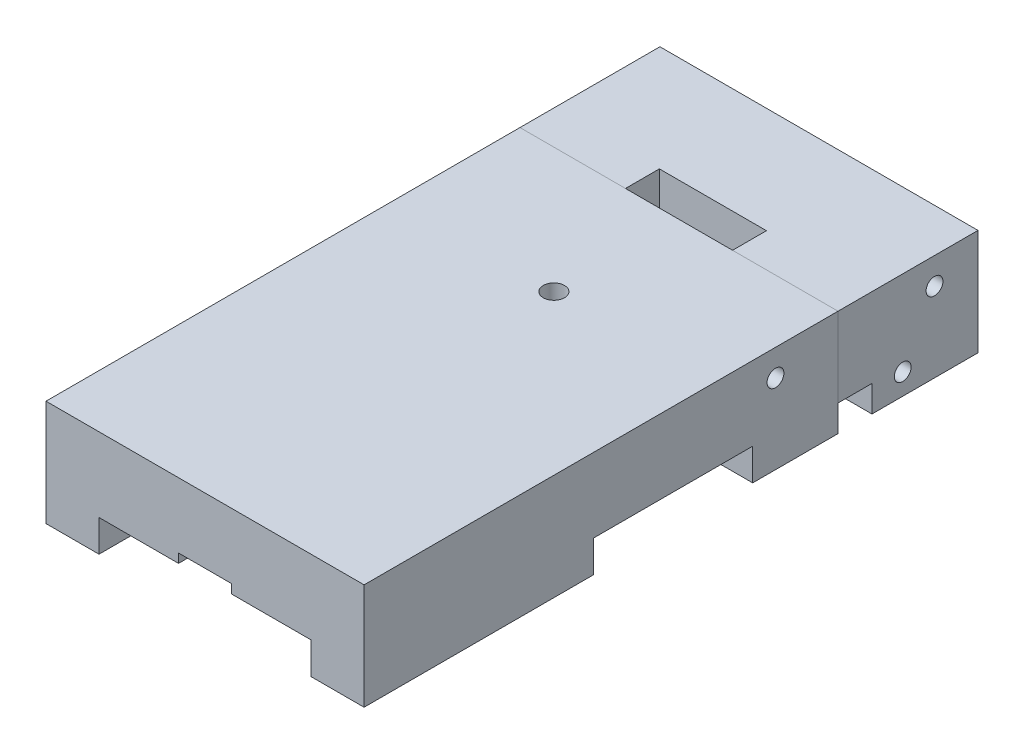
SolidWorks part; units mm, degrees
material "Nylon 6/10"
ref_plane "Front Plane" through (0, 0, 0) normal (0, 0, 1) x (1, 0, 0)
ref_plane "Top Plane" through (0, 0, 0) normal (0, 1, 0) x (1, 0, 0)
ref_plane "Right Plane" through (0, 0, 0) normal (1, 0, 0) x (0, 0, -1)
sketch "Sketch1" plane through (0, 0, 0) normal (0, 1, 0) x (1, 0, 0)
  line L1 (-38.1, -73.533) -> (38.1, -73.533)
  line L2 (-38.1, -73.533) -> (-38.1, 73.533)
  line L3 (-38.1, 73.533) -> (38.1, 73.533)
  line L4 (38.1, -73.533) -> (38.1, 73.533)
  line L5 (-38.1, -73.533) -> (38.1, 73.533) construction
  line L6 (-38.1, 73.533) -> (38.1, -73.533) construction
  point P0 (0, 0)
  dimension "D1" = 76.2
  dimension "D2" = 147.066
extrude "Boss-Extrude1" add sketch "Sketch1" along normal blind 12.7 and the other way blind 12.7
sketch "Sketch2" plane through (0, 0, -73.533) normal (0, 0, -1) x (-1, 0, 0)
  line L1 (-38.1, -12.7) -> (38.1, -12.7) construction
  circle A0 centre (0, -12.7) radius 4.7625
  dimension "D1" = 9.525
extrude "Cut-Extrude1" cut sketch "Sketch2" against normal blind 25.4
ref_plane "Plane1" through (0, -12.7, 0) normal (0, -1, 0) x (-1, 0, 0)
sketch "Sketch3" plane through (0, -12.7, 0) normal (0, -1, 0) x (-1, 0, 0)
  line L0 (10.922, 19.558) -> (44.45, 19.558)
  line L1 (-19.05, -83.058) -> (19.05, -83.058)
  line L2 (-25.4, -76.708) -> (-25.4, -18.542)
  line L3 (0, 0) -> (0, 102.0916) construction
  line L4 (25.4, -76.708) -> (25.4, -18.542)
  line L5 (-10.922, 19.558) -> (-10.922, 40.005)
  line L6 (25.4, -18.542) -> (44.45, -18.542)
  line L7 (-10.922, 40.005) -> (10.922, 40.005)
  line L8 (10.922, 19.558) -> (10.922, 40.005)
  line L10 (-44.45, -18.542) -> (-25.4, -18.542)
  line L11 (-44.45, -18.542) -> (-44.45, 19.558)
  line L12 (-44.45, 19.558) -> (-10.922, 19.558)
  line L13 (44.45, -18.542) -> (44.45, 19.558)
  line L14 (4.7625, 73.533) -> (4.7625, 48.133)
  line L15 (4.7625, 48.133) -> (-4.7625, 48.133)
  line L16 (-4.7625, 48.133) -> (-4.7625, 73.533)
  line L17 (-4.7625, 73.533) -> (-38.1, 73.533)
  line L18 (-38.1, 73.533) -> (-38.1, -73.533)
  line L19 (-38.1, -73.533) -> (38.1, -73.533)
  line L20 (38.1, -73.533) -> (38.1, 73.533)
  line L21 (38.1, 73.533) -> (4.7625, 73.533)
  line L25 (-4.7625, 73.533) -> (-38.1, 73.533) construction
  line L26 (-38.1, 73.533) -> (-38.1, -73.533) construction
  line L27 (-38.1, -73.533) -> (38.1, -73.533) construction
  line L28 (38.1, -73.533) -> (38.1, 73.533) construction
  line L29 (38.1, 73.533) -> (4.7625, 73.533) construction
  arc A0 (-25.4, -76.708) -> (-19.05, -83.058) centre (-19.05, -76.708) ccw
  arc A1 (19.05, -83.058) -> (25.4, -76.708) centre (19.05, -76.708) ccw
  dimension "D5" = 6.35
  dimension "D6" = 21.844
  dimension "D8" = 19.05
  dimension "D9" = 20.447
  dimension "D2" = 25.4
  dimension "D3" = 25.4
  dimension "D4" = 9.525
  dimension "D7" = 38.1
  dimension "D10" = 53.975
  dimension "D1" = 0
extrude "Cut-Extrude2" cut sketch "Sketch3" against normal blind 7.62
sketch "Sketch5" plane through (0, 0, 0) normal (0, 1, 0) x (1, 0, 0)
  line L0 (-4.7625, 73.533) -> (-38.1, 73.533) construction
  line L1 (12.827, 48.133) -> (-12.827, 48.133)
  line L2 (12.827, 40.005) -> (12.827, 48.133)
  line L3 (12.827, 40.005) -> (-12.827, 40.005)
  line L4 (0, 0) -> (0, 121.8983) construction
  line L6 (-12.827, 40.005) -> (-12.827, 48.133)
  point P17 (12.827, 40.005)
  point P20 (12.827, 48.133)
  dimension "D1" = 8.128
  dimension "D2" = 25.654
  dimension "D4" = 25.4
extrude "Cut-Extrude4" cut sketch "Sketch5" along normal through all and the other way through all
hole_wizard "1/4-20 Tapped Hole1" positions "Sketch8" profile "Sketch7" tap size "1/4-20" standard "ANSI Inch"
sketch "Sketch8" plane through (-11.0345, 12.7, 14.5475) normal (0, -1, 0) x (-1, 0, 0)
  line L1 (-23.8615, 62.6805) -> (1.7925, 62.6805) construction
  point P0 (-11.0345, 24.5805)
  dimension "D1" = 38.1
  dimension "D2" = 0
sketch "Sketch7" plane through (0, 12.7, -10.033) normal (1, 0, 0) x (0, 0, 1)
  line L0 (0, 0) -> (0, 20.5838)
  line L1 (0, 20.5838) -> (2.5527, 19.05)
  line L2 (2.5527, 19.05) -> (2.5527, 0)
  line L5 (2.5527, 0) -> (0, 0)
  line L10 (0, 20.5838) -> (-2.5527, 19.05) construction
  line L11 (0, -6.35) -> (0, 107.95) construction
  dimension "Tap Drill Dia." = 5.1054
  dimension "Tap Drill Depth" = 19.05
  dimension "Drill Angle" = 118
cosmetic thread "Hole Thread2" parameters "D1"=9.525, "D2"=6.35
sketch "Sketch9" plane through (0, -12.7, 0) normal (0, -1, 0) x (-1, 0, 0)
  line L0 (38.1, -28.067) -> (25.4, -28.067) construction
  line L1 (38.1, -18.542) -> (38.1, -73.533) construction
  line L2 (25.4, -73.533) -> (25.4, -18.542) construction
  line L3 (25.4, -18.542) -> (38.1, -18.542) construction
  line L4 (38.1, 29.083) -> (25.4, 29.083) construction
  line L5 (38.1, 73.533) -> (38.1, 19.558) construction
  line L6 (-10.922, 19.558) -> (-38.1, 19.558) construction
  line L7 (0, 0) -> (0, 53.9724) construction
  circle A0 centre (31.75, 29.083) radius 1.5964
  circle A1 centre (31.75, -28.067) radius 1.5964
  circle A2 centre (-31.75, -28.067) radius 1.5964
  circle A3 centre (-31.75, 29.083) radius 1.5964
  dimension "D1" = 9.525
  dimension "D2" = 3.1928
  dimension "D3" = 9.525
extrude "8-32 Tapped Hole" cut sketch "Sketch9" against normal blind 12.7
ref_plane "Plane2" through (0, 0, -19.558) normal (0, 0, 1) x (1, 0, 0)
ref_plane "Plane3" through (0, -5.08, 0) normal (0, -1, 0) x (-1, 0, 0)
sketch "Sketch11" plane through (0, -5.08, 0) normal (0, -1, 0) x (-1, 0, 0)
  line L1 (25.4, -73.533) -> (-25.4, -73.533) construction
  line L2 (0.0025, -32.893) -> (-0.0025, -32.893)
  line L3 (6.35, -39.2405) -> (6.35, -73.533)
  line L4 (6.35, -73.533) -> (-6.35, -73.533)
  line L5 (-6.35, -39.2405) -> (-6.35, -73.533)
  line L6 (6.35, -32.893) -> (-6.35, -73.533) construction
  line L7 (6.35, -73.533) -> (-6.35, -32.893) construction
  line L8 (0, -53.213) -> (0, -73.533) construction
  arc A0 (-0.0025, -32.893) -> (-6.35, -39.2405) centre (-0.0025, -39.2405) ccw
  arc A1 (0.0025, -32.893) -> (6.35, -39.2405) centre (0.0025, -39.2405) cw
  point P0 (0, -53.213)
  dimension "D2" = 6.3475
  dimension "D1" = 12.7
  dimension "D3" = 40.64
extrude "Cut-Extrude7" cut sketch "Sketch11" against normal blind 2.159
sketch "Sketch12" plane through (0, -5.08, 0) normal (0, -1, 0) x (1, 0, 0)
  line L0 (0, 0) -> (0, 79.2462) construction
  line L1 (-25.4, 73.533) -> (-6.35, 73.533) construction
  circle A0 centre (12.7, 54.483) radius 2.0193
  circle A1 centre (-12.7, 54.483) radius 2.0193
  dimension "D1" = 4.0386
  dimension "D2" = 25.4
  dimension "D3" = 19.05
extrude "Cut-Extrude8" cut sketch "Sketch12" against normal blind 12.7
sketch "Sketch13" plane through (0, -12.7, 0) normal (0, -1, 0) x (1, 0, 0)
  line L0 (38.1, -19.558) -> (38.1, -73.533) construction
  line L1 (12.827, -40.005) -> (38.1, -40.005)
  line L2 (12.827, -40.005) -> (12.827, -48.133)
  line L3 (12.827, -48.133) -> (38.1, -48.133)
  line L4 (38.1, -40.005) -> (38.1, -48.133)
  line L5 (12.827, -48.133) -> (4.7625, -48.133) construction
extrude "Cut-Extrude9" cut sketch "Sketch13" against normal blind 6.35
ref_plane "Plane4" through (0, 0, -40.005) normal (0, 0, -1) x (-1, 0, 0)
sketch "Sketch15" plane through (0, 0, -73.533) normal (0, 0, -1) x (-1, 0, 0)
  line L0 (-38.1, 0) -> (38.1, 0) construction
  line L1 (-38.1, -12.7) -> (-38.1, 12.7) construction
  line L2 (38.1, -12.7) -> (38.1, 12.7) construction
  circle A0 centre (-24.13, 0) radius 2.0193
  circle A1 centre (24.13, 0) radius 2.0193
  dimension "D1" = 4.0386
  dimension "D3" = 13.97
  dimension "D2" = 13.97
extrude "Cut-Extrude11" cut sketch "Sketch15" against normal blind 57.15
sketch "Sketch17" plane through (0, 0, -73.533) normal (0, 0, -1) x (-1, 0, 0)
  line L0 (-38.1, 0) -> (38.1, 0) construction
  line L3 (38.1, -12.7) -> (38.1, 12.7) construction
  circle A0 centre (-24.13, 0) radius 4.2164
  circle A1 centre (24.13, 0) radius 4.2164
  circle A3 centre (24.13, 0) radius 2.0193 construction
  circle A4 centre (-24.13, 0) radius 2.0193 construction
  dimension "D1" = 8.4328
extrude "Cut-Extrude12" cut sketch "Sketch17" against normal blind 5.461
sketch "Sketch19" plane through (0, -12.7, 0) normal (0, -1, 0) x (1, 0, 0)
  line L1 (-4.7625, -73.533) -> (-38.1, -73.533) construction
  line L2 (-38.1, -73.533) -> (-38.1, -19.558) construction
  circle A0 centre (-31.75, -56.4388) radius 2.0193
  circle A1 centre (-12.7, -56.4388) radius 2.0193
  dimension "D1" = 4.0386
  dimension "D2" = 17.0942
  dimension "D3" = 6.35
  dimension "D4" = 19.05
extrude "Cut-Extrude14" cut sketch "Sketch19" against normal blind 12.7
sketch "Sketch22" plane through (0, -12.7, 0) normal (0, -1, 0) x (1, 0, 0)
  line L0 (-12.7, -32.5755) -> (12.7, -32.5755) construction
  line L1 (-12.7, -21.9075) -> (12.7, -21.9075) construction
  line L2 (-12.7, -33.3692) -> (12.7, -33.3692)
  line L3 (-12.7, -31.7817) -> (12.7, -31.7817)
  line L4 (-12.7, -21.1137) -> (12.7, -21.1137)
  line L5 (-12.7, -22.7012) -> (12.7, -22.7012)
  line L6 (0, -39.4682) -> (0, -19.7785) construction
  line L7 (10.922, -27.2415) -> (-10.922, -27.2415) construction
  line L8 (10.922, -40.005) -> (10.922, -19.558) construction
  line L9 (-10.922, -19.558) -> (-10.922, -40.005) construction
  arc A0 (-12.7, -21.1137) -> (-12.7, -22.7012) centre (-12.7, -21.9075) ccw
  arc A1 (12.7, -22.7012) -> (12.7, -21.1137) centre (12.7, -21.9075) ccw
  arc A2 (-12.7, -33.3692) -> (-12.7, -31.7817) centre (-12.7, -32.5755) cw
  arc A3 (12.7, -31.7817) -> (12.7, -33.3692) centre (12.7, -32.5755) cw
  point P6 (0, -21.9075)
  point P12 (10.922, -29.7815)
  point P17 (0, -32.5755)
  dimension "D1" = 1.5875
  dimension "D2" = 25.4
  dimension "D3" = 10.668
  dimension "D4" = 2.54
extrude "Cut-Extrude16" cut sketch "Sketch22" against normal blind 2.286
sketch "Sketch23" plane through (0, -12.7, 0) normal (0, -1, 0) x (1, 0, 0)
  line L1 (-10.922, -40.005) -> (10.922, -40.005)
  line L2 (-10.922, -40.005) -> (-10.922, -22.733)
  line L3 (-7.747, -19.558) -> (7.747, -19.558)
  line L4 (10.922, -40.005) -> (10.922, -22.733)
  arc A0 (-7.747, -19.558) -> (-10.922, -22.733) centre (-7.747, -22.733) ccw
  arc A1 (7.747, -19.558) -> (10.922, -22.733) centre (7.747, -22.733) cw
  point P9 (10.922, -19.558)
  dimension "D1" = 3.175
extrude "Cut-Extrude18" cut sketch "Sketch23" against normal blind 11.176
sketch "Sketch25" plane through (38.1, 0, 0) normal (1, 0, 0) x (0, 0, -1)
  line L0 (-73.533, 12.7) -> (73.533, 12.7) construction
  line L1 (73.533, -12.7) -> (73.533, 12.7) construction
  point P0 (63.119, 6.35)
  point P1 (55.499, -7.62)
  point P2 (25.019, 6.35)
  dimension "D1" = 7.62
  dimension "D2" = 13.97
  dimension "D3" = 38.1
  dimension "D4" = 6.35
  dimension "D5" = 10.414
hole_wizard "#10-32 Tapped Hole1" positions "Sketch29" profile "Sketch28" tap size "#10-32" standard "ANSI Inch"
sketch "Sketch29" plane through (38.1, 0, 0) normal (1, 0, 0) x (0, 0, -1)
  point P0 (63.119, 6.35)
  point P3 (55.499, -7.62)
  point P6 (25.019, 6.35)
sketch "Sketch28" plane through (38.1, 6.35, -63.119) normal (0, 1, 0) x (0, 0, -1)
  line L0 (0, 0) -> (0, 15.3357)
  line L1 (0, 15.3357) -> (2.0193, 14.1224)
  line L2 (2.0193, 14.1224) -> (2.0193, 0)
  line L5 (2.0193, 0) -> (0, 0)
  line L10 (0, 15.3357) -> (-2.0193, 14.1224) construction
  line L11 (0, -6.35) -> (0, 107.95) construction
  dimension "Tap Drill Dia." = 4.0386
  dimension "Tap Drill Depth" = 14.1224
  dimension "Drill Angle" = 118
cosmetic thread "Hole Thread3" parameters "D1"=10.16, "D2"=4.826
cosmetic thread "Hole Thread4" parameters "D1"=10.16, "D2"=4.826
cosmetic thread "Hole Thread5" parameters "D1"=10.16, "D2"=4.826
split "Split1" trim tools "Plane4" bodies to split 126 resulting bodies 124 125
